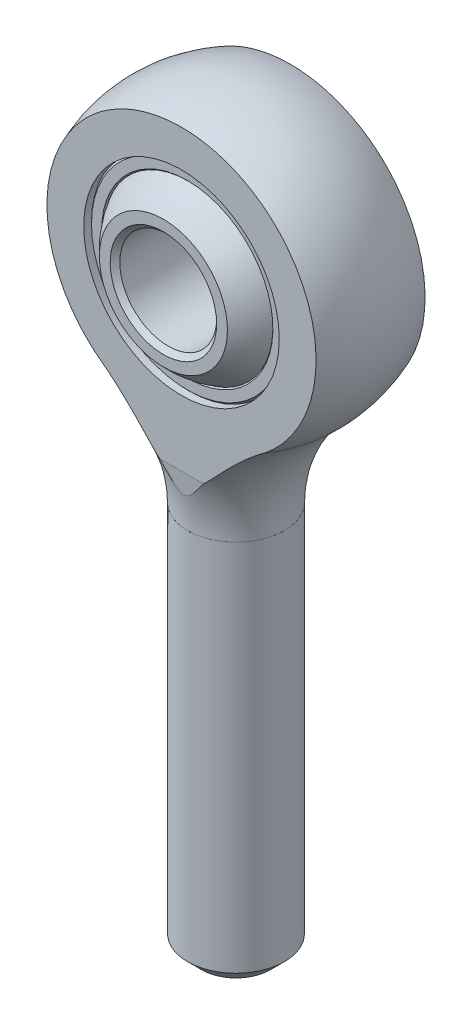
SolidWorks part; units mm, degrees
ref_plane "Front" through (0, 0, 0) normal (0, 0, 1) x (1, 0, 0)
ref_plane "Top" through (0, 0, 0) normal (0, 1, 0) x (1, 0, 0)
ref_plane "Right" through (0, 0, 0) normal (1, 0, 0) x (0, 0, -1)
sketch "Sketch1" plane through (0, 0, 0) normal (0, 0, 1) x (1, 0, 0)
  line L0 (0, 0) -> (0, -25.4)
  line L1 (0, -25.4) -> (3.175, -25.4)
  line L2 (3.175, -25.4) -> (3.175, 0)
  line L3 (3.175, 0) -> (0, 0)
  line L5 (0, 23.8125) -> (0, 0) construction
  line L6 (0, 23.8125) -> (9.525, 23.8125) construction
  line L7 (9.525, 23.8125) -> (9.525, 14.2875) construction
  line L8 (-3.175, -25.4) -> (-3.175, 0) construction
  arc A0 (6.3827, 7.2174) -> (0, 23.8125) centre (0, 14.2875) ccw construction
  circle A1 centre (0, 14.2875) radius 3.175 construction
  circle A2 centre (0, 14.2875) radius 6.35 construction
  circle A3 centre (0, 14.2875) radius 6.4135 construction
  arc A4 (3.175, 0) -> (6.3827, 7.2174) centre (12.8984, 0) cw construction
  point P16 (-3.175, -19.2768)
  dimension "A" = 6.35
  dimension "Ball Dia" = 12.7
  dimension "B" = 19.05
  dimension "D1" = 12.827
  dimension "D" = 39.6875
  dimension "E" = 25.4
  dimension "Thread Dia" = 6.35
  dimension "D2" = 6.1232
revolve "Revolve1" add sketch "Sketch1" angle 360 about L5
sketch "Sketch12" [suppressed] plane through (0, -25.4, 0) normal (0, -1, 0) x (1, 0, 0)
  circle A1 centre (0, 0) radius 3.175
  circle A2 centre (0, 0) radius 3.175
  dimension "D1" = 0
chamfer "Chamfer2" distance 0.9071 angle 45 1 edges at (-3.175, -25.4, 0)
sketch "Sketch4" plane through (0, 0, 0) normal (0, 0, 1) x (1, 0, 0)
  line L0 (3.175, 0) -> (0, 0) construction
  line L2 (0, 23.8125) -> (0, 0) construction
  line L3 (3.175, 0) -> (0, 0)
  line L5 (0, 23.8125) -> (0, 0)
  line L6 (0, 23.8125) -> (0, 26.3525) construction
  arc A0 (6.3827, 7.2174) -> (0, 23.8125) centre (0, 14.2875) ccw construction
  arc A1 (6.3827, 7.2174) -> (0, 23.8125) centre (0, 14.2875) ccw
  arc A2 (6.3827, 7.2174) -> (3.175, 0) centre (12.8984, 0) ccw construction
  arc A3 (6.3827, 7.2174) -> (3.175, 0) centre (12.8984, 0) ccw
  dimension "D1" = 2.54
revolve "Revolve2" add sketch "Sketch4" angle 360 about L6
sketch "Sketch5" plane through (0, 0, 0) normal (1, 0, 0) x (0, 0, -1)
  line L0 (3.575, 23.8125) -> (9.525, 23.8125)
  line L1 (-3.575, 23.8125) -> (3.575, 23.8125) construction
  line L2 (-3.575, 23.8125) -> (-3.575, 3.575)
  line L3 (-3.175, 0) -> (3.175, 0) construction
  line L4 (3.575, 23.8125) -> (3.575, 3.575)
  line L5 (9.525, 23.8125) -> (9.525, 0)
  line L6 (9.525, 0) -> (3.175, 0)
  line L7 (-3.175, 0) -> (-9.525, 0)
  line L8 (-9.525, 0) -> (-9.525, 23.8125)
  line L9 (-9.525, 23.8125) -> (-3.575, 23.8125)
  line L10 (3.175, 0) -> (3.575, 3.575)
  line L11 (-3.175, 0) -> (-3.575, 3.575)
  line L12 (-3.575, 3.575) -> (3.575, 3.575) construction
  line L13 (0, 0) -> (0, 3.575) construction
  arc A0 (6.3827, 7.2174) -> (-6.3827, 7.2174) centre (0, 14.2875) ccw construction
  dimension "F" = 7.1501
  dimension "D2" = 3.575
  dimension "D1" = 6.35
extrude "Cut-Extrude1" cut sketch "Sketch5" against normal through all and the other way through all
sketch "Sketch6" plane through (0, 0, 0) normal (0, 0, 1) x (1, 0, 0)
  circle A0 centre (0, 14.2875) radius 6.4135 construction
  circle A1 centre (0, 14.2875) radius 6.4135
extrude "Cut-Extrude2" cut sketch "Sketch6" against normal through all and the other way through all
sketch "Sketch7" plane through (0, 0, 0) normal (0, 0, 1) x (1, 0, 0)
  line L0 (0, 20.6375) -> (0, 7.9375)
  line L1 (0, 23.8125) -> (0, 0) construction
  line L2 (0, 0) -> (0, 7.9375) construction
  arc A0 (0, 7.9375) -> (0, 20.6375) centre (0, 14.2875) ccw
  circle A1 centre (0, 14.2875) radius 6.35 construction
revolve "Revolve3" add sketch "Sketch7" angle 360 about L2
sketch "Sketch8" plane through (0, 0, 0) normal (1, 0, 0) x (0, 0, -1)
  line L0 (-3.575, 23.8125) -> (3.575, 23.8125) construction
  line L1 (-4.7625, 23.8125) -> (4.7625, 23.8125) construction
  line L2 (-4.7625, 23.8125) -> (-4.7625, 0)
  line L3 (-4.7625, 0) -> (4.7625, 0) construction
  line L4 (4.7625, 23.8125) -> (4.7625, 0)
  line L5 (4.7625, 23.8125) -> (9.525, 23.8125)
  line L6 (9.525, 23.8125) -> (9.525, 0)
  line L7 (9.525, 0) -> (4.7625, 0)
  line L8 (-4.7625, 0) -> (-9.525, 0)
  line L9 (-9.525, 0) -> (-9.525, 23.8125)
  line L10 (-9.525, 23.8125) -> (-4.7625, 23.8125)
  dimension "C" = 9.525
extrude "Cut-Extrude3" cut sketch "Sketch8" against normal through all and the other way through all
sketch "Sketch10" plane through (0, 0, 0) normal (0, 0, 1) x (1, 0, 0)
  circle A0 centre (0, 14.2875) radius 3.175 construction
  circle A1 centre (0, 14.2875) radius 3.175
extrude "Cut-Extrude4" cut sketch "Sketch10" against normal through all and the other way through all
chamfer "Chamfer1" distance 0.3175 angle 45 2 edges at (3.175, 14.2875, -4.7625) (3.175, 14.2875, 4.7625)
sketch "Sketch14" plane through (0, 0, 0) normal (1, 0, 0) x (0, 0, -1)
  line L0 (-3.1941, 20.701) -> (-3.194, 19.7757)
  line L1 (-3.1941, 20.701) -> (-1.5437, 20.701)
  line L2 (-1.5437, 20.701) -> (-1.5437, 20.447)
  line L3 (3.194, 19.7757) -> (3.1941, 20.701)
  line L4 (3.1941, 20.701) -> (1.5437, 20.701)
  line L5 (1.5437, 20.701) -> (1.5437, 20.447)
  line L8 (-4.7625, 14.2875) -> (4.7625, 14.2875) construction
  line L9 (-4.7625, 18.4876) -> (-4.7625, 10.0874) construction
  line L10 (3.575, 20.701) -> (-3.575, 20.701) construction
  line L11 (-3.575, 23.1161) -> (-3.575, 7.2174) construction
  arc A1 (3.194, 19.7757) -> (1.5437, 20.447) centre (0, 14.2875) ccw
  arc A2 (-1.5437, 20.447) -> (-3.194, 19.7757) centre (0, 14.2875) ccw
  arc A3 (4.7625, 18.4876) -> (-4.7625, 18.4876) centre (0, 14.2875) ccw construction
  dimension "D1" = 0.381
  dimension "D2" = 0.254
revolve "Revolve4" add sketch "Sketch14" angle 360 about L8
chamfer "Chamfer3" distance 0.127 angle 45 2 edges at (0, 7.874, 3.194) (0, 8.7993, 3.194) first distance on face at (0, 7.874, 3.194) first distance on face at (0, 8.7993, 3.194)
chamfer "Chamfer4" distance 0.127 angle 45 2 edges at (0, 8.7993, -3.1941) (0, 7.874, -3.1941) first distance on face at (0, 8.7993, -3.1941) first distance on face at (0, 7.874, -3.1941)
sketch "Sketch11" plane through (0, 0, 0) normal (1, 0, 0) x (0, 0, -1)
  line L0 (0, 14.2875) -> (-4.7625, 14.9568) construction
  line L1 (3.575, 14.2875) -> (-3.575, 14.2875) construction
  line L2 (0, 14.2875) -> (-4.7625, 13.6182) construction
  line L3 (0, 23.8125) -> (0, 0) construction
  line L4 (-4.7625, 23.8125) -> (-4.7625, 0) construction
  line L5 (0, 14.2875) -> (0.0074, 14.2875) construction
  dimension "Swivel" = 16
curve "Helix/Spiral1" [suppressed] pitch 0.9071 height 26.6236 turns 29.3488 parameters "pitch"=0.9071
sketch "Sketch13" [suppressed] plane through (0, 0, 0) normal (1, 0, 0) x (0, 0, -1)
  line L0 (-3.175, -26.1937) -> (-3.175, -25.4)
  line L1 (-3.175, -25.4) -> (-2.5858, -25.7402)
  line L2 (-2.5858, -25.7402) -> (-2.5858, -25.8536)
  line L3 (-2.5858, -25.8536) -> (-3.175, -26.1937)
  line L4 (-2.5858, -25.7969) -> (-3.175, -25.7969) construction
  line L5 (-2.8804, -26.0237) -> (-2.8804, -25.5701) construction
  line L6 (-3.175, -25.4) -> (3.175, -25.4) construction
  dimension "D1" = 0.1134
  dimension "D2" = 0.4536
  dimension "D3" = 60
sweep "Cut-Sweep1" [suppressed] cut profiles "Sketch13" path "Helix/Spiral1"
sketch "Sketch15" [suppressed] plane through (0, 0, 0) normal (0, -1, 0) x (1, 0, 0)
  arc A2 (0, -3.175) -> (0, 3.175) centre (0, 0) ccw
  arc A3 (0, 3.175) -> (0, -3.175) centre (0, 0) ccw
  arc A5 (0, 3.175) -> (0, -3.175) centre (0, 0) ccw
  arc A6 (0, -3.175) -> (0, 3.175) centre (0, 0) ccw
  dimension "D1" = 0
extrude "Boss-Extrude1" [suppressed] add sketch "Sketch15" along normal up to next draft 20
ref_axis "Center Axis 1" through (0, 14.2875, -1.17) along (0, 0, 1)
ref_axis "Center Axis 2" through (0, 29.9353, 0) along (0, -1, 0)
ref_point "Point2"
equation "\"D1@Sketch1\"=\"Ball Dia@Sketch1\"*1.01"
equation "\"D1@Chamfer1\"=\"A@Sketch1\"/20"
equation "\"D1@Sketch5\"=\"Thread Dia@Sketch1\""
equation "\"D2@Sketch5\"=\"F@Sketch5\"/2"
equation "\"D1@Sketch13\" = \"pitch@Helix/Spiral1\"*.125"
equation "\"D2@Sketch13\" = \"pitch@Helix/Spiral1\"*.50"
equation "\"D1@Chamfer2\" = \"pitch@Helix/Spiral1\""
equation "\"D2@Sketch1\" = \"pitch@Helix/Spiral1\"*6.750"
equation "\"D3@Helix/Spiral1\"=\"E@Sketch1\"+\"pitch@Helix/Spiral1\"+.0124578"
